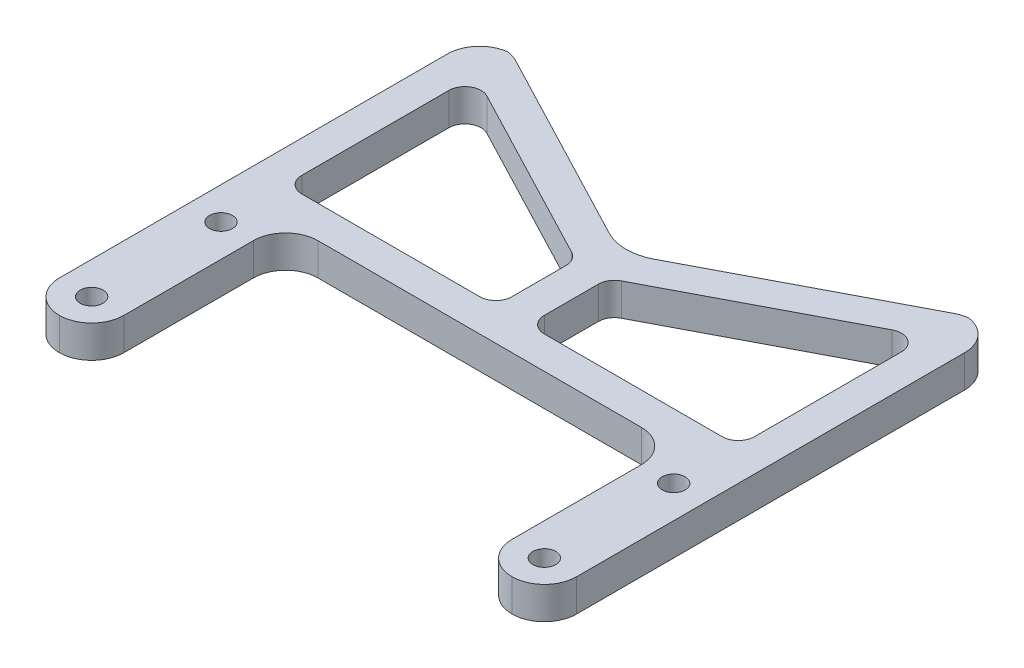
SolidWorks part; units mm, degrees
material "Custom Plastic"
ref_plane "Front Plane" through (0, 0, 0) normal (0, 0, 1) x (1, 0, 0)
ref_plane "Top Plane" through (0, 0, 0) normal (0, 1, 0) x (1, 0, 0)
ref_plane "Right Plane" through (0, 0, 0) normal (1, 0, 0) x (0, 0, -1)
sketch "Sketch1" plane through (0, 0, 0) normal (0, 1, 0) x (1, 0, 0)
  line L1 (-50.8, -44.45) -> (50.8, -44.45)
  line L2 (-50.8, -44.45) -> (-50.8, 44.45)
  line L3 (-50.8, 44.45) -> (50.8, 44.45)
  line L4 (50.8, -44.45) -> (50.8, 44.45)
  line L5 (-50.8, -44.45) -> (50.8, 44.45) construction
  line L6 (-50.8, 44.45) -> (50.8, -44.45) construction
  point P0 (0, 0)
  dimension "D1" = 101.6
  dimension "D2" = 88.9
extrude "Base" add sketch "Sketch1" along normal blind 6.35
sketch "Sketch2" plane through (0, 6.35, 0) normal (0, 1, 0) x (1, 0, 0)
  line L0 (-44.45, 44.45) -> (0, 21.2052)
  line L1 (50.8, 44.45) -> (-50.8, 44.45) construction
  line L2 (0, 21.2052) -> (44.45, 44.45)
  line L3 (-44.45, 44.45) -> (44.45, 44.45)
  line L4 (0, 0) -> (0, 44.45) construction
  circle A0 centre (0, 30.1625) radius 7.9375 construction
  dimension "D1" = 15.875
  dimension "D2" = 88.9
  dimension "D3" = 14.2875
extrude "Tube notch" cut sketch "Sketch2" against normal through all
sketch "Sketch3" plane through (0, 6.35, 0) normal (0, 1, 0) x (1, 0, 0)
  line L1 (0, 0) -> (0, -44.45) construction
  line L2 (-44.45, -12.7) -> (44.45, -12.7) construction
  line L3 (-44.45, -12.7) -> (-44.45, -38.1) construction
  line L4 (-44.45, -38.1) -> (44.45, -38.1) construction
  line L5 (44.45, -12.7) -> (44.45, -38.1) construction
  line L6 (-50.8, -44.45) -> (50.8, -44.45) construction
  line L7 (-50.8, -6.35) -> (50.8, -6.35) construction
  line L8 (-50.8, 44.45) -> (-50.8, -44.45) construction
  line L9 (50.8, -44.45) -> (50.8, 44.45) construction
  point P9 (0, -12.7)
  dimension "D1" = 88.9
  dimension "D2" = 6.35
  dimension "D3" = 25.4
  dimension "D4" = 6.35
hole_wizard "Mounting holes" positions "Sketch5" profile "Sketch4" hole size "#8" standard "ANSI Inch" end condition through all
sketch "Sketch5" plane through (0, 6.35, 0) normal (0, 1, 0) x (1, 0, 0)
  point P0 (-44.45, -12.7)
  point P3 (-44.45, -38.1)
  point P6 (44.45, -38.1)
  point P9 (44.45, -12.7)
sketch "Sketch4" plane through (-44.45, 6.35, 12.7) normal (1, 0, 0) x (0, 0, 1)
  line L0 (0, 0) -> (0, 6.35)
  line L1 (0, 6.35) -> (2.2479, 6.35)
  line L2 (2.2479, 6.35) -> (2.2479, 0)
  line L5 (2.2479, 0) -> (0, 0)
  line L11 (0, -6.35) -> (0, 107.95) construction
  dimension "Thru Hole Dia." = 4.4958
  dimension "Thru Hole Depth" = 6.35
sketch "Sketch8" plane through (0, 6.35, 0) normal (0, 1, 0) x (1, 0, 0)
  line L0 (-50.8, -44.45) -> (50.8, -44.45) construction
  line L1 (-38.1, -44.45) -> (38.1, -44.45)
  line L2 (-38.1, -44.45) -> (-38.1, -6.35)
  line L3 (-38.1, -6.35) -> (38.1, -6.35)
  line L4 (38.1, -44.45) -> (38.1, -6.35)
  point P6 (0, -6.35)
  dimension "D1" = 38.1
  dimension "D2" = 76.2
extrude "Wheel cutout" cut sketch "Sketch8" against normal through all
fillet "Fillet1" radius 6.35 10 edges at (-50.8, 3.175, 44.45) (-44.45, 3.175, -44.45) (44.45, 3.175, -44.45) (50.8, 3.175, -44.45) (50.8, 3.175, 44.45) (38.1, 3.175, 44.45) (38.1, 3.175, 6.35) (-38.1, 3.175, 6.35) (-38.1, 3.175, 44.45) (-50.8, 3.175, -44.45)
fillet "Fillet2" radius 9.525 1 edges at (0, 3.175, -21.2052)
sketch "Sketch9" plane through (0, 6.35, 0) normal (0, 1, 0) x (1, 0, 0)
  line L0 (-44.45, 0) -> (-44.45, 37.2841)
  line L1 (-44.45, 37.2841) -> (-3.175, 15.6997)
  line L2 (3.175, 15.6997) -> (44.45, 37.2841)
  line L3 (44.45, 37.2841) -> (44.45, 0)
  line L4 (44.45, 0) -> (3.175, 0)
  line L5 (-43.0675, 43.727) -> (-4.4139, 23.5134) construction
  line L6 (-50.8, 38.1) -> (-50.8, -38.1) construction
  line L7 (31.75, -6.35) -> (-31.75, -6.35) construction
  line L8 (-3.175, 15.6997) -> (-3.175, 0)
  line L9 (3.175, 15.6997) -> (3.175, 0)
  line L10 (-3.175, 0) -> (-44.45, 0)
  line L11 (4.4139, 23.5134) -> (43.0675, 43.727) construction
  line L12 (50.8, -38.1) -> (50.8, 38.1) construction
  point P2 (0, 0)
  point P9 (0, 0)
  dimension "D1" = 6.35
  dimension "D2" = 6.35
  dimension "D3" = 6.35
  dimension "D4" = 6.35
  dimension "D5" = 6.35
extrude "Cut-Extrude1" cut sketch "Sketch9" against normal through all
fillet "Fillet3" radius 3.175 8 edges at (-44.45, 3.175, 0) (-3.175, 3.175, -15.6997) (-3.175, 3.175, 0) (44.45, 3.175, 0) (3.175, 3.175, 0) (3.175, 3.175, -15.6997) (44.45, 3.175, -37.2841) (-44.45, 3.175, -37.2841)
equation "\"MAT_THICKNESS\"=0.1"
